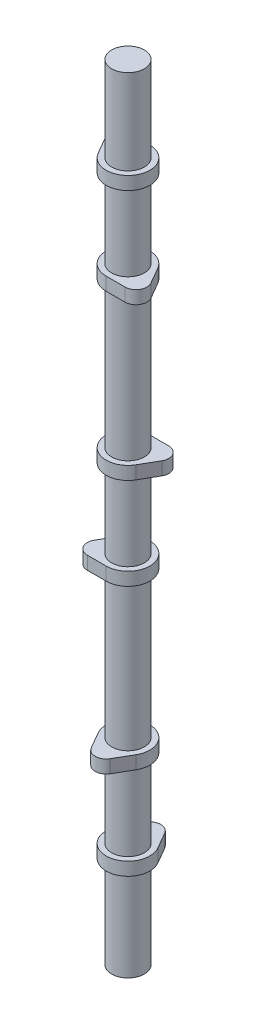
SolidWorks part; units mm, degrees
note: '?' marks a value the reader was unsure of.
ref_plane "Front Plane" through (0, 0, 0) normal (0, 0, 1) x (1, 0, 0)
ref_plane "Top Plane" through (0, 0, 0) normal (0, 1, 0) x (1, 0, 0)
ref_plane "Right Plane" through (0, 0, 0) normal (1, 0, 0) x (0, 0, -1)
sketch "Sketch2" plane through (0, 0, 0) normal (0, 1, 0) x (1, 0, 0)
  line L0 (-10.9985, 6.35) -> (-5.4993, 15.875)
  line L1 (5.4993, 15.875) -> (10.9985, 6.35)
  arc A0 (-10.9985, 6.35) -> (10.9985, 6.35) centre (0, 0) ccw
  arc A1 (5.4993, 15.875) -> (-5.4993, 15.875) centre (0, 12.7) ccw
  dimension "D2" = 12.7
  dimension "D3" = 25.4
  dimension "D1" = 12.7
extrude "Boss-Extrude1" add sketch "Sketch2" along normal blind 7.62
ref_axis "Axis1" through (0, 36.8015, 0) along (0, -1, 0)?
pattern_linear "LPattern3" count 2 spacing 53.34 along (0, 1, 0) of bodies 101
move or copy body "Body-Move/Copy1" bodies to move or copy 102 copy no rotation origin (0, 0, 0) rotation axis (0, 1, 0) rotation angle 180
pattern_linear "LPattern5" count 3 spacing 146.05 along (0, 1, 0) of bodies 103 101
move or copy body "Body-Move/Copy2" bodies to move or copy 110 108 copy no rotation origin (0, 0, 0) rotation axis (0, 1, 0) rotation angle 120
move or copy body "Body-Move/Copy3" bodies to move or copy 111 109 copy no rotation origin (0, 0, 0) rotation axis (0, -1, 0) rotation angle 120
sketch "Sketch3" plane through (0, 353.06, 0) normal (0, 1, 0) x (1, 0, 0)
  circle A0 centre (0, 0) radius 9.5
  dimension "D1" = 19
extrude "Boss-Extrude2" add sketch "Sketch3" against normal blind 456.09 from offset 49.53
